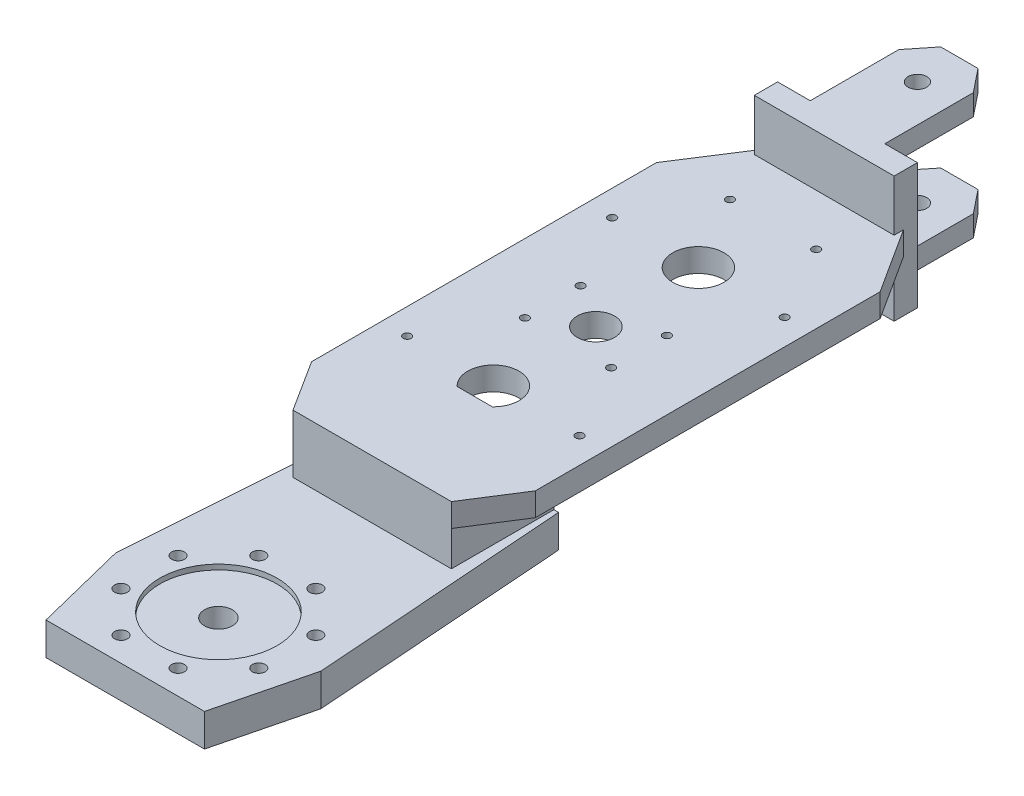
SolidWorks part; units mm, degrees
material "6061-T6 (SS)"
ref_plane "Front Plane" through (0, 0, 0) normal (0, 0, 1) x (1, 0, 0)
ref_plane "Top Plane" through (0, 0, 0) normal (0, 1, 0) x (1, 0, 0)
ref_plane "Right Plane" through (0, 0, 0) normal (1, 0, 0) x (0, 0, -1)
ref_plane "PL_Knee_Plate_base" through (0, -34, 0) normal (0, 1, 0) x (1, 0, 0)
sketch "SK_Knee_Plate" plane through (0, -34, 0) normal (0, 1, 0) x (1, 0, 0)
  line L0 (-34, -40) -> (34, -40)
  line L1 (34, -40) -> (44, 0)
  line L2 (44, 0) -> (36, 110)
  line L3 (36, 110) -> (-36, 110)
  line L4 (-36, 110) -> (-44, 0)
  line L5 (-44, 0) -> (-34, -40)
  circle A0 centre (29.5641, 12.2459) radius 2.75
  circle A1 centre (12.2459, 29.5641) radius 2.75
  circle A2 centre (-12.2459, 29.5641) radius 2.75
  circle A3 centre (-29.5641, 12.2459) radius 2.75
  circle A4 centre (-29.5641, -12.2459) radius 2.75
  circle A5 centre (-12.2459, -29.5641) radius 2.75
  circle A6 centre (12.2459, -29.5641) radius 2.75
  circle A7 centre (29.5641, -12.2459) radius 2.75
  circle A8 centre (0, 0) radius 6
  dimension "D11_SK_Knee_Plate" = 5.5
  dimension "D14_SK_Knee_Plate" = 5.5
  dimension "D17_SK_Knee_Plate" = 5.5
  dimension "D20_SK_Knee_Plate" = 5.5
  dimension "D23_SK_Knee_Plate" = 5.5
  dimension "D26_SK_Knee_Plate" = 5.5
  dimension "D29_SK_Knee_Plate" = 5.5
  dimension "D32_SK_Knee_Plate" = 5.5
  dimension "D35_SK_Knee_Plate" = 12
  dimension "P1" = 34
  dimension "P2" = 40
  dimension "P3" = 34
  dimension "P4" = 40
  dimension "P5" = 44
  dimension "P6" = 36
  dimension "P7" = 110
  dimension "P8" = 36
  dimension "P9" = 110
  dimension "P10" = 44
  dimension "P12" = 29.5641
  dimension "P13" = 12.2459
  dimension "P15" = 12.2459
  dimension "P16" = 29.5641
  dimension "P18" = 12.2459
  dimension "P19" = 29.5641
  dimension "P21" = 29.5641
  dimension "P22" = 12.2459
  dimension "P24" = 29.5641
  dimension "P25" = 12.2459
  dimension "P27" = 12.2459
  dimension "P28" = 29.5641
  dimension "P30" = 12.2459
  dimension "P31" = 29.5641
  dimension "P33" = 29.5641
  dimension "P34" = 12.2459
extrude "Knee_Plate" add sketch "SK_Knee_Plate" along normal blind 14
ref_plane "PL_Knee_Pilot_Recess_base" through (0, -20, 0) normal (0, 1, 0) x (1, 0, 0)
sketch "SK_Knee_Pilot_Recess" plane through (0, -20, 0) normal (0, 1, 0) x (1, 0, 0)
  circle A0 centre (0, 0) radius 25.15
  dimension "D1_SK_Knee_Pilot_Recess" = 50.3
extrude "Knee_Pilot_Recess" cut sketch "SK_Knee_Pilot_Recess" against normal blind 2.2
ref_plane "PL_Joggle_base" through (0, 0, -110) normal (0, 0, 1) x (1, 0, 0)
sketch "SK_Joggle" plane through (0, 0, -110) normal (0, 0, 1) x (1, 0, 0)
  line L0 (-34, -34) -> (34, -34)
  line L1 (34, -34) -> (34, 5)
  line L2 (34, 5) -> (-34, 5)
  line L3 (-34, 5) -> (-34, -34)
  dimension "P1" = 34
  dimension "P2" = 34
  dimension "P3" = 34
  dimension "P4" = 34
  dimension "P5" = 34
  dimension "P6" = 5
  dimension "P7" = 34
  dimension "P8" = 5
extrude "Joggle" add sketch "SK_Joggle" along normal blind 44
ref_plane "PL_Web_base" through (0, -5, 0) normal (0, 1, 0) x (1, 0, 0)
sketch "SK_Web" plane through (0, -5, 0) normal (0, 1, 0) x (1, 0, 0)
  line L0 (-34, 66) -> (34, 66)
  line L1 (34, 66) -> (48, 88)
  line L2 (48, 88) -> (48, 236)
  line L3 (48, 236) -> (30, 264)
  line L4 (30, 264) -> (-30, 264)
  line L5 (-30, 264) -> (-48, 236)
  line L6 (-48, 236) -> (-48, 88)
  line L7 (-48, 88) -> (-34, 66)
  circle A0 centre (37, 118) radius 1.7
  circle A1 centre (18.5, 150.0429) radius 1.7
  circle A2 centre (-18.5, 150.0429) radius 1.7
  circle A3 centre (-37, 118) radius 1.7
  circle A4 centre (-18.5, 85.9571) radius 1.7
  circle A5 centre (18.5, 85.9571) radius 1.7
  circle A6 centre (37, 206) radius 1.7
  circle A7 centre (18.5, 238.0429) radius 1.7
  circle A8 centre (-18.5, 238.0429) radius 1.7
  circle A9 centre (-37, 206) radius 1.7
  circle A10 centre (-18.5, 173.9571) radius 1.7
  circle A11 centre (18.5, 173.9571) radius 1.7
  circle A12 centre (0, 118) radius 11
  circle A13 centre (0, 206) radius 11
  circle A14 centre (0, 162) radius 8
  dimension "D17_SK_Web" = 3.4
  dimension "D20_SK_Web" = 3.4
  dimension "D23_SK_Web" = 3.4
  dimension "D26_SK_Web" = 3.4
  dimension "D29_SK_Web" = 3.4
  dimension "D32_SK_Web" = 3.4
  dimension "D35_SK_Web" = 3.4
  dimension "D38_SK_Web" = 3.4
  dimension "D41_SK_Web" = 3.4
  dimension "D44_SK_Web" = 3.4
  dimension "D47_SK_Web" = 3.4
  dimension "D50_SK_Web" = 3.4
  dimension "D53_SK_Web" = 22
  dimension "D55_SK_Web" = 22
  dimension "D57_SK_Web" = 16
  dimension "P1" = 34
  dimension "P2" = 66
  dimension "P3" = 34
  dimension "P4" = 66
  dimension "P5" = 48
  dimension "P6" = 88
  dimension "P7" = 48
  dimension "P8" = 236
  dimension "P9" = 30
  dimension "P10" = 264
  dimension "P11" = 30
  dimension "P12" = 264
  dimension "P13" = 48
  dimension "P14" = 236
  dimension "P15" = 48
  dimension "P16" = 88
  dimension "P18" = 37
  dimension "P19" = 118
  dimension "P21" = 18.5
  dimension "P22" = 150.0429
  dimension "P24" = 18.5
  dimension "P25" = 150.0429
  dimension "P27" = 37
  dimension "P28" = 118
  dimension "P30" = 18.5
  dimension "P31" = 85.9571
  dimension "P33" = 18.5
  dimension "P34" = 85.9571
  dimension "P36" = 37
  dimension "P37" = 206
  dimension "P39" = 18.5
  dimension "P40" = 238.0429
  dimension "P42" = 18.5
  dimension "P43" = 238.0429
  dimension "P45" = 37
  dimension "P46" = 206
  dimension "P48" = 18.5
  dimension "P49" = 173.9571
  dimension "P51" = 18.5
  dimension "P52" = 173.9571
  dimension "P54" = 118
  dimension "P56" = 206
  dimension "P58" = 162
extrude "Web" add sketch "SK_Web" along normal blind 10
ref_plane "PL_Fork_Bar_base" through (0, 0, -270) normal (0, 0, 1) x (1, 0, 0)
sketch "SK_Fork_Bar" plane through (0, 0, -270) normal (0, 0, 1) x (1, 0, 0)
  line L0 (-30, -27) -> (30, -27)
  line L1 (30, -27) -> (30, 27)
  line L2 (30, 27) -> (-30, 27)
  line L3 (-30, 27) -> (-30, -27)
  dimension "P1" = 30
  dimension "P2" = 27
  dimension "P3" = 30
  dimension "P4" = 27
  dimension "P5" = 30
  dimension "P6" = 27
  dimension "P7" = 30
  dimension "P8" = 27
extrude "Fork_Bar" add sketch "SK_Fork_Bar" along normal blind 10
ref_plane "PL_Tine_Lat_base" through (0, 18, 0) normal (0, 1, 0) x (1, 0, 0)
sketch "SK_Tine_Lat" plane through (0, 18, 0) normal (0, 1, 0) x (1, 0, 0)
  line L0 (-16, 260) -> (16, 260)
  line L1 (16, 260) -> (16, 308)
  line L2 (16, 308) -> (8, 318)
  line L3 (8, 318) -> (-8, 318)
  line L4 (-8, 318) -> (-16, 308)
  line L5 (-16, 308) -> (-16, 260)
  circle A0 centre (0, 300) radius 4
  dimension "D13_SK_Tine_Lat" = 8
  dimension "P1" = 16
  dimension "P2" = 260
  dimension "P3" = 16
  dimension "P4" = 260
  dimension "P5" = 16
  dimension "P6" = 308
  dimension "P7" = 8
  dimension "P8" = 318
  dimension "P9" = 8
  dimension "P10" = 318
  dimension "P11" = 16
  dimension "P12" = 308
  dimension "P14" = 300
extrude "Tine_Lat" add sketch "SK_Tine_Lat" along normal blind 9
ref_plane "PL_Tine_Med_base" through (0, -27, 0) normal (0, 1, 0) x (1, 0, 0)
sketch "SK_Tine_Med" plane through (0, -27, 0) normal (0, 1, 0) x (1, 0, 0)
  line L0 (-16, 260) -> (16, 260)
  line L1 (16, 260) -> (16, 308)
  line L2 (16, 308) -> (8, 318)
  line L3 (8, 318) -> (-8, 318)
  line L4 (-8, 318) -> (-16, 308)
  line L5 (-16, 308) -> (-16, 260)
  circle A0 centre (0, 300) radius 4
  dimension "D13_SK_Tine_Med" = 8
  dimension "P1" = 16
  dimension "P2" = 260
  dimension "P3" = 16
  dimension "P4" = 260
  dimension "P5" = 16
  dimension "P6" = 308
  dimension "P7" = 8
  dimension "P8" = 318
  dimension "P9" = 8
  dimension "P10" = 318
  dimension "P11" = 16
  dimension "P12" = 308
  dimension "P14" = 300
extrude "Tine_Med" add sketch "SK_Tine_Med" along normal blind 9
ref_plane "PL_AnkleZ" through (0, 0, -300) normal (0, 0, 1) x (1, 0, 0)
ref_axis "AX_AnklePitch" through (0, 30.05, -300) along (0, -1, 0)
ref_axis "AX_KneeY" through (0, 30.05, 0) along (0, -1, 0)
ref_plane "PL_KneeRef" through (0, 0, 0) normal (-0.9239, 0, 0.3827) x (0, -1, 0)
equation "\"Shin_length\"= 300"
equation "\"AnkleA_z\"= -118"
equation "\"AnkleB_z\"= -206"
